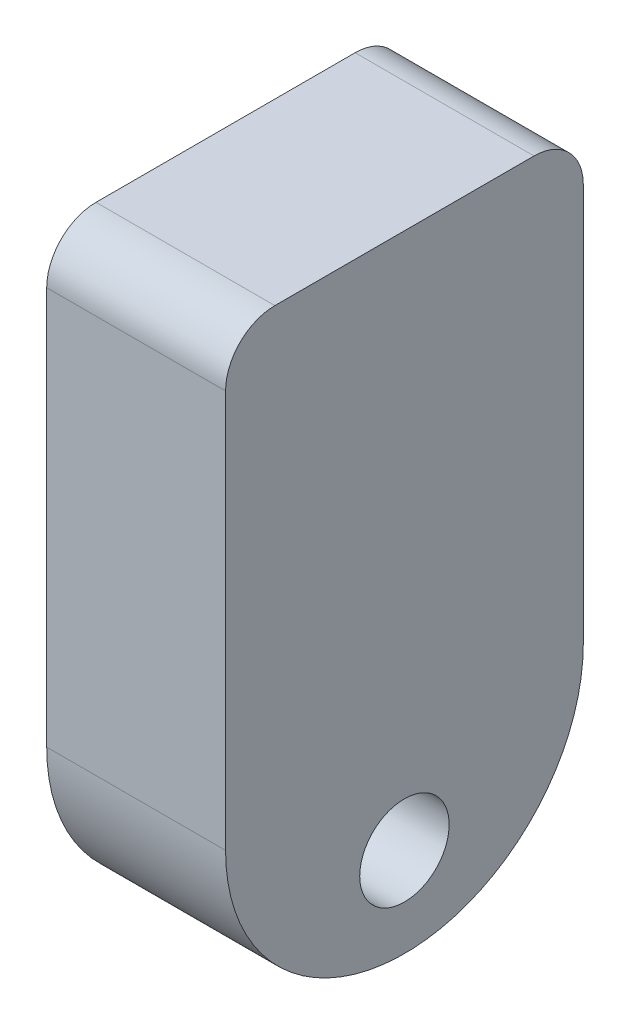
SolidWorks part; units mm, degrees
ref_plane "Front Plane" through (0, 0, 0) normal (0, 0, 1) x (1, 0, 0)
ref_plane "Top Plane" through (0, 0, 0) normal (0, 1, 0) x (1, 0, 0)
ref_plane "Right Plane" through (0, 0, 0) normal (1, 0, 0) x (0, 0, -1)
sketch "Sketch1" plane through (0, 0, 0) normal (1, 0, 0) x (0, 0, -1)
  line L0 (25.4, 88.9) -> (25.4, 63.5) construction
  line L1 (0, 0) -> (50.8, 0)
  line L2 (0, 0) -> (0, 88.9)
  line L3 (0, 88.9) -> (50.8, 88.9)
  line L4 (50.8, 0) -> (50.8, 88.9)
  circle A0 centre (25.4, 63.5) radius 6.35
  dimension "D4" = 12.7
  dimension "D1" = 50.8
  dimension "D2" = 88.9
  dimension "D3" = 25.4
extrude "Boss-Extrude1" add sketch "Sketch1" along normal blind 25.4
sketch "Sketch2" plane through (25.4, 0, 0) normal (1, 0, 0) x (0, 0, -1)
  circle A0 centre (25.4, 63.5) radius 6.35
extrude "Boss-Extrude2" add sketch "Sketch2" against normal blind 1
sketch "Sketch3" plane through (25.4, 0, 0) normal (1, 0, 0) x (0, 0, -1)
  line L0 (0, 0) -> (0, 25.4) construction
  line L1 (0, 88.9) -> (0, 0) construction
  line L2 (0, 25.4) -> (50.8, 25.4) construction
  line L3 (50.8, 0) -> (50.8, 88.9) construction
  line L4 (0, 25.4) -> (50.8, 25.4)
  arc A0 (0, 25.4) -> (50.8, 25.4) centre (25.4, 25.4) ccw
  line M2 (0, 88.9) -> (0, 0)
  line M3 (0, 0) -> (50.8, 0)
  line M4 (50.8, 0) -> (50.8, 88.9)
  dimension "D1" = 25.4
extrude "Cut-Extrude1" cut sketch "Sketch3" against normal through all both and the other way through all contours A0 M3 M4 | A0 M2 M3 region at (25.4, 5.6735, -5.6735) region at (25.4, 5.6735, -45.1265)
sketch "Sketch4" plane through (25.4, 0, 0) normal (1, 0, 0) x (0, 0, -1)
  line L0 (0, 25.4) -> (50.8, 25.4)
  line L1 (25.4, 25.4) -> (25.4, 0)
  arc A0 (0, 25.4) -> (50.8, 25.4) centre (25.4, 25.4) ccw construction
  circle A1 centre (25.4, 12.7) radius 6.35
  dimension "D1" = 12.7
extrude "Cut-Extrude2" cut sketch "Sketch4" against normal blind 24.4 and the other way through all contours L1 A1 | L1 A1 region at (25.4, 12.7, -28.095) region at (25.4, 12.7, -22.705)
fillet "Fillet1" radius 7 2 edges at (12.7, 88.9, -50.8) (12.7, 88.9, 0)
